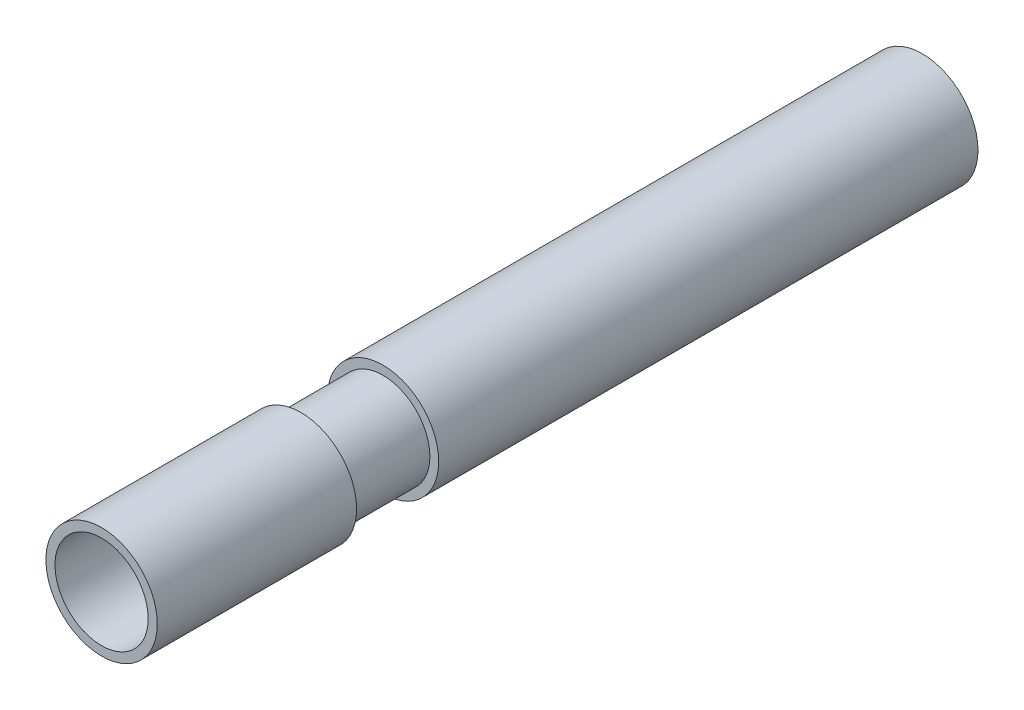
SolidWorks part; units mm, degrees
other "Markup1"
sketch "Sketch6"
material "Brass"
ref_plane "Front Plane" through (0, 0, 0) normal (0, 0, 1) x (1, 0, 0)
ref_plane "Top Plane" through (0, 0, 0) normal (0, 1, 0) x (1, 0, 0)
ref_plane "Right Plane" through (0, 0, 0) normal (1, 0, 0) x (0, 0, -1)
sketch "Sketch1" plane through (0, 0, 0) normal (1, 0, 0) x (0, 0, -1)
  line L0 (0, 0) -> (35.56, 0) construction
  line L1 (0, 0) -> (0, 2.413)
  line L2 (0, 2.413) -> (8.636, 2.413)
  line L3 (8.636, 2.413) -> (8.636, 2.032)
  line L4 (8.636, 2.032) -> (12.192, 2.032)
  line L5 (12.192, 2.032) -> (12.192, 2.413)
  line L6 (12.192, 2.413) -> (35.56, 2.413)
  line L7 (35.56, 2.413) -> (35.56, 0)
  line L8 (35.56, 0) -> (0, 0)
  dimension "D1" = 2.413
  dimension "D2" = 35.56
  dimension "D3" = 0.381
  dimension "D4" = 3.556
  dimension "D5" = 8.636
revolve "Revolve1" add sketch "Sketch1" angle 360 about L0
ref_plane "Plane1" through (0, 0, 0) normal (0, 0, 1) x (1, 0, 0)
sketch "Sketch2" plane through (0, 0, 0) normal (0, 0, 1) x (1, 0, 0)
  circle A0 centre (0, 0) radius 2.0193
  dimension "D1" = 4.0386
extrude "Cut-Extrude2" cut sketch "Sketch2" against normal through all
ref_plane "Plane3" through (0, 0, -30.48) normal (0, 0, -1) x (-1, 0, 0)
sketch "Sketch10" plane through (0, 0, -30.48) normal (0, 0, -1) x (-1, 0, 0)
  circle A0 centre (0, 0) radius 2.0193 construction
  circle A1 centre (0, 0) radius 2.0193
curve "Helix/Spiral1" pitch 0.5292 height 3.7042 radius 2.0193 centre (0, 0, -30.48) axis (0, 0, 1) start towards (1, 0, 0)
sketch "Sketch12" plane through (0, 0, -30.48) normal (0, 0, -1) x (-1, 0, 0)
  line L1 (-1.726, 0) -> (-2.1659, 0.254)
  line L2 (-2.1659, 0.254) -> (-2.1659, -0.254)
  line L3 (-2.1659, -0.254) -> (-1.726, 0)
  circle A0 centre (-2.0193, 0) radius 0.1466 construction
  dimension "D1" = 0.254
sweep "Cut-Sweep1" cut profiles "Sketch12" path "Helix/Spiral1" align with end faces yes
